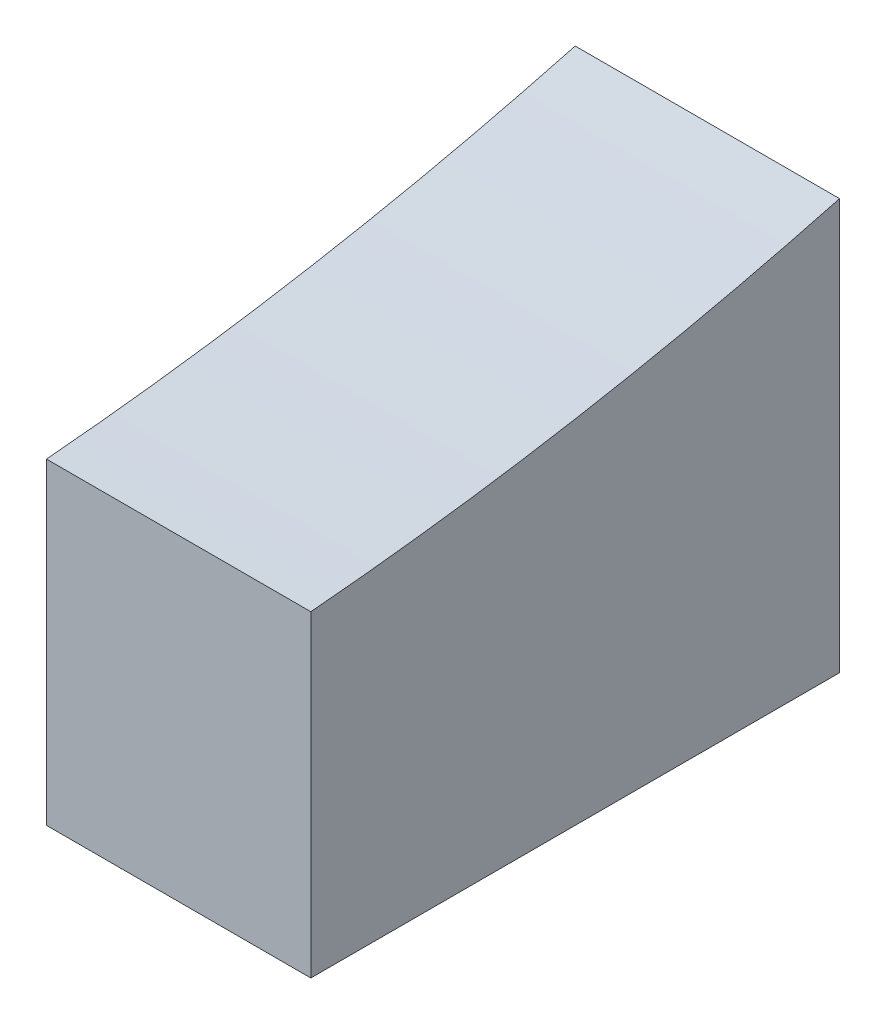
SolidWorks part; units mm, degrees
ref_plane "前视基准面" through (0, 0, 0) normal (0, 0, 1) x (1, 0, 0)
ref_plane "上视基准面" through (0, 0, 0) normal (0, 1, 0) x (1, 0, 0)
ref_plane "右视基准面" through (0, 0, 0) normal (1, 0, 0) x (0, 0, -1)
other "Configuration Table"
sketch "草图1" plane through (0, 0, 0) normal (1, 0, 0) x (0, 0, -1)
  line L9 (10, 12) -> (10, 0)
  line L10 (10, 0) -> (30, 0)
  line L11 (30, 15.5325) -> (30, 0)
  arc A1 (10, 12) -> (30, 15.5325) centre (0, 127) ccw
  dimension "D3" = 20
  dimension "D6" = 12
extrude "凸台-拉伸1" add sketch "草图1" along normal blind 10
extrude "凸台-拉伸2" add sketch "草图1<2>" along normal blind 10
sketch "草图1<2>" plane through (0, 0, 0) normal (1, 0, 0) x (0, 0, -1) same geometry as "草图1"
sketch "草图2" plane through (0, 0, 0) normal (0, -1, 0) x (1, 0, 0)
  line L0 (10, -10) -> (0, -10) construction
  line L1 (0, -10) -> (0, -30) construction
  circle A0 centre (5, -18) radius 3
  dimension "D1" = 8
  dimension "D2" = 5
extrude "切除-拉伸1" cut sketch "草图2" against normal blind 10
cosmetic thread "装饰螺纹线1" parameters "D1"=5, "D2"=7
